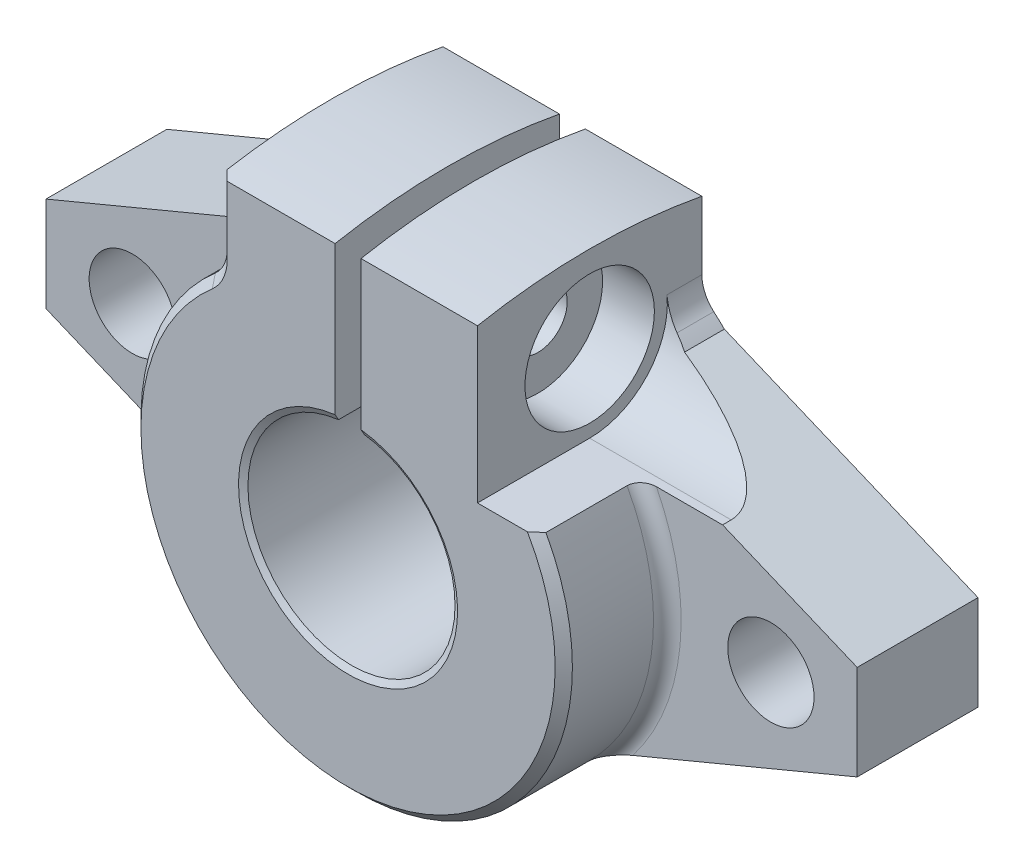
SolidWorks part; units mm, degrees
material "1060 Alloy"
ref_plane "Front Plane" through (0, 0, 0) normal (0, 0, 1) x (1, 0, 0)
ref_plane "Top Plane" through (0, 0, 0) normal (0, 1, 0) x (1, 0, 0)
ref_plane "Right Plane" through (0, 0, 0) normal (1, 0, 0) x (0, 0, -1)
sketch "Sketch1" plane through (0, 0, 0) normal (0, 0, 1) x (1, 0, 0)
  line L0 (0, 23.6454) -> (0, -19.4549) construction
  line L1 (0.75, 5.9529) -> (0.75, 15.5)
  line L2 (0.75, 15.5) -> (7.5, 15.5)
  line L3 (7.5, 15.5) -> (7.5, 10)
  line L4 (-7.5, 15.5) -> (-7.5, 10)
  line L5 (-0.75, 15.5) -> (-7.5, 15.5)
  line L6 (-0.75, 5.9529) -> (-0.75, 15.5)
  arc A0 (-0.75, 5.9529) -> (0.75, 5.9529) centre (0, 0) ccw
  arc A1 (-7.5, 10) -> (7.5, 10) centre (0, 0) ccw
  arc A2 (0, -6) -> (0.818, 5.944) centre (0, 0) ccw construction
  arc A3 (0, -12.5) -> (1.7041, 12.3833) centre (0, 0) ccw construction
  dimension "D1" = 6
  dimension "D3" = 1.5
  dimension "D4" = 15
  dimension "D5" = 28
  dimension "D2" = 6.5
extrude "Boss-Extrude1" add sketch "Sketch1" along normal blind 13
sketch "Sketch2" plane through (0, 0, 0) normal (1, 0, 0) x (0, 0, -1)
  line L0 (0, 10) -> (0, 15.5) construction
  line L1 (-13, 10) -> (-13, 15.5) construction
  line L2 (-6.5, 15.5) -> (-6.5, -4.9716) construction
  line L3 (-13, 15.5) -> (0, 15.5) construction
  arc A0 (0, 14.8911) -> (-13, 14.8911) centre (-6.5, -19.5) ccw
  dimension "D1" = 35
extrude "Cut-Extrude1" cut sketch "Sketch2" against normal through all and the other way through all flip side to cut
fillet "Fillet1" radius 2 2 edges at (-7.5, 10, 6.5) (7.5, 10, 6.5)
sketch "Sketch3" plane through (0, 0, 0) normal (0, 0, 1) x (1, 0, 0)
  line L0 (0, 19.2448) -> (0, 0) construction
  line L1 (0, 0) -> (32.3729, 0) construction
  line L2 (8.8035, 8.874) -> (23.5, 2.75)
  line L3 (23.5, 2.75) -> (23.5, -2.75)
  line L4 (8.8035, -8.874) -> (23.5, -2.75)
  line L5 (-23.5, 2.75) -> (-23.5, -2.75) construction
  arc A0 (-8.1897, 9.4435) -> (8.1897, 9.4435) centre (0, 0) ccw construction
  arc A1 (8.8035, 8.874) -> (8.8035, -8.874) centre (0, 0) cw
  arc A2 (-8.1897, 9.4435) -> (8.1897, 9.4435) centre (0, 0) ccw construction
  point P11 (23.5, 0)
  point P12 (18.5, 0)
  point P15 (-18.5, 0)
  dimension "D1" = 47
  dimension "D2" = 37
  dimension "D3" = 5.5
extrude "Boss-Extrude2" add sketch "Sketch3" along normal blind 7
mirror "Mirror1" about plane through (0, 0, 0) normal (1, 0, 0) of bodies 103
hole_wizard "Диаметр отверстия Ø5.0 (5)1" positions "Sketch5" profile "Sketch4" hole size "Ø5.0" standard "DIN"
sketch "Sketch5" plane through (0, 0, 7) normal (0, 0, 1) x (1, 0, 0)
  point P0 (18.5, 0)
  point P2 (-18.5, 0)
sketch "Sketch4" plane through (18.5, 0, 7) normal (1, 0, 0) x (0, -1, 0)
  line L0 (0, 0) -> (0, 11.5022)
  line L1 (0, 11.5022) -> (2.5, 10)
  line L2 (2.5, 10) -> (2.5, 0)
  line L5 (2.5, 0) -> (0, 0)
  line L10 (0, 11.5022) -> (-2.5, 10) construction
  line L11 (0, -6.35) -> (0, 107.95) construction
  dimension "Диаметр отверстия" = 5
  dimension "Глубина отверстия" = 10
  dimension "Угол заточки сверла" = 118
sketch "Sketch6" plane through (0, 0, 0) normal (1, 0, 0) x (0, 0, -1)
  line L0 (-6.5, -12.5) -> (-6.5, 18.0939) construction
  line L1 (-13, -12.5) -> (0, -12.5) construction
  arc A1 (0, 14.8911) -> (-13, 14.8911) centre (-6.5, -19.5) ccw construction
  point P0 (-6.5, 10.5)
  dimension "D1" = 5
sketch "Sketch9" plane through (7.5, 0, 0) normal (1, 0, 0) x (0, 0, -1)
  line L0 (-6.5, -12.5) -> (-6.5, 18.0939) construction
  line L2 (-13, 10.9545) -> (0, 10.9545) construction
  line L3 (-2.023, 10.9545) -> (-13, 10.9545)
  line L4 (-13, 10.9545) -> (-13, 6)
  line L5 (-13, 9.4435) -> (-13, -12.5) construction
  line L6 (-13, 6) -> (-6.5, 6)
  arc A0 (-6.5, 6) -> (-2.023, 10.9545) centre (-6.5, 10.5) ccw
  dimension "D1" = 4.5
extrude "Cut-Extrude2" cut sketch "Sketch9" along normal up to next
hole_wizard "CBORE for M4 Hex Socket Head Cap Screw3" positions "Sketch11" profile "Sketch10" counterbore size "M4" standard "DIN" end condition through all
sketch "Sketch11" plane through (7.5, 0, 0) normal (1, 0, 0) x (0, 0, -1)
  point P0 (-6.5, 10.5)
sketch "Sketch10" plane through (7.5, 10.5, 6.5) normal (0, 1, 0) x (0, 0, -1)
  line L0 (0, 0) -> (0, 31)
  line L1 (0, 31) -> (1.7, 31)
  line L3 (1.7, 31) -> (1.7, 3)
  line L4 (1.7, 3) -> (3.75, 3)
  line L5 (3.75, 3) -> (3.75, 0)
  line L7 (3.75, 0) -> (0, 0)
  line L11 (0, -6.35) -> (0, 107.95) construction
  dimension "Thru Hole Dia." = 3.4
  dimension "Thru Hole Depth" = 31
  dimension "C'Bore Dia." = 7.5
  dimension "C'Bore Depth" = 3
ref_plane "Plane1" through (0, 0, 6.5) normal (0, 0, 1) x (1, 0, 0)
sketch "Sketch12" plane through (0, 0, 6.5) normal (0, 0, 1) x (1, 0, 0)
  line L0 (0, 10.5) -> (19.7633, 10.5) construction
  line L1 (4.5, 14) -> (8.5, 14)
  line L2 (8.5, 14) -> (8.5, 10.5)
  line L3 (8.5, 10.5) -> (-5.5, 10.5)
  line L4 (-5.5, 10.5) -> (-5.5, 12)
  line L5 (-5.5, 12) -> (-5, 12.5)
  line L6 (-5, 12.5) -> (4.5, 12.5)
  line L7 (4.5, 12.5) -> (4.5, 14)
  line L8 (4.5, 7) -> (8.5, 7) construction
  line L9 (-5, 8.5) -> (4.5, 8.5) construction
  line L10 (4.5, 8.8) -> (4.5, 12.2) construction
  line L11 (4.5, 8.8) -> (4.5, 12.2) construction
  dimension "D1" = 7
  dimension "D2" = 4
  dimension "D3" = 4
  dimension "D4" = 0.5
  dimension "D5" = 10
  dimension "D6" = 45
chamfer "Chamfer2" distance 0.5 angle 45 3 edges at (-7.5, 12.9228, 13) (-7.6806, 10.124, 13) (-2.2116, -12.3028, 13)
fillet "Fillet2" radius 0.8 4 edges at (-12.5, 0, 7) (8.8035, -8.874, 3.5) (-8.8035, -8.874, 3.5) (12.37, -1.7983, 7)
chamfer "Chamfer3" distance 0.2 angle 60 1 edges at (0, -6, 13) first distance on face at (0, -0.0235, 6.5)
